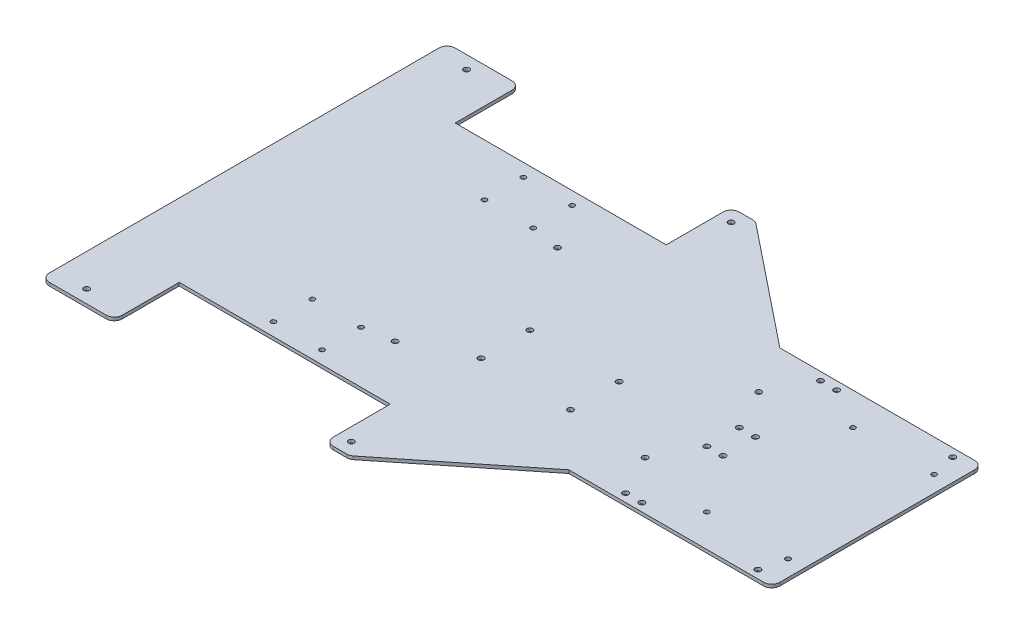
SolidWorks part; units mm, degrees
ref_plane "정면" through (0, 0, 0) normal (0, 0, 1) x (1, 0, 0)
ref_plane "윗면" through (0, 0, 0) normal (0, 1, 0) x (1, 0, 0)
ref_plane "우측면" through (0, 0, 0) normal (1, 0, 0) x (0, 0, -1)
sketch "스케치1" plane through (0, 0, 0) normal (0, 1, 0) x (1, 0, 0)
  line L1 (-195, -125) -> (195, -125)
  line L2 (-195, -125) -> (-195, 125)
  line L3 (-195, 125) -> (195, 125)
  line L4 (195, -125) -> (195, 125)
  line L5 (-195, -125) -> (195, 125) construction
  line L6 (-195, 125) -> (195, -125) construction
  point P0 (0, 0)
  dimension "D1" = 390
  dimension "D2" = 250
extrude "보스-돌출1" add sketch "스케치1" along normal blind 2
sketch "스케치2" plane through (0, 2, 0) normal (0, 1, 0) x (1, 0, 0)
  line L5 (195, 125) -> (-195, 125) construction
  line L6 (-150, 125) -> (-20, 125)
  line L7 (-150, 125) -> (-150, 85)
  line L8 (-150, 85) -> (-20, 85)
  line L9 (-20, 125) -> (-20, 85)
  line L10 (-150, -125) -> (-20, -125)
  line L11 (-150, -125) -> (-150, -85)
  line L12 (-150, -85) -> (-20, -85)
  line L13 (-20, -125) -> (-20, -85)
  line L14 (-195, -125) -> (195, -125) construction
  line L15 (70, 125) -> (195, 125)
  line L16 (70, 125) -> (70, 65)
  line L17 (70, 65) -> (195, 65)
  line L18 (195, 125) -> (195, 65)
  line L19 (70, -125) -> (195, -125)
  line L20 (70, -125) -> (70, -65)
  line L21 (70, -65) -> (195, -65)
  line L22 (195, -125) -> (195, -65)
  line L23 (195, -125) -> (195, 125) construction
  line L24 (-195, 125) -> (-195, -125) construction
  dimension "D1" = 130
  dimension "D2" = 40
  dimension "D3" = 40
  dimension "D4" = 60
  dimension "D5" = 60
  dimension "D6" = 45
  dimension "D7" = 125
extrude "컷-돌출1" cut sketch "스케치2" against normal blind 5
sketch "스케치3" plane through (0, 2, 0) normal (0, 1, 0) x (1, 0, 0)
  line L0 (-5, 125) -> (70, 65)
  line L2 (70, -65) -> (-5, -125)
  line L4 (-5, 125) -> (70, 125)
  line L5 (-5, -125) -> (70, -125)
  line L6 (70, -65) -> (70, -125)
  line L7 (70, 65) -> (70, 125)
  dimension "D1" = 75
  dimension "D2" = 75
extrude "컷-돌출2" cut sketch "스케치3" against normal blind 10
fillet "필렛1" radius 5 10 edges at (-20, 1, 125) (-20, 1, -125) (-5, 1, 125) (-5, 1, -125) (195, 1, -65) (195, 1, 65) (-195, 1, -125) (-195, 1, 125) (-150, 1, -125) (-150, 1, 125)
sketch "스케치4" plane through (0, 2, 0) normal (0, 1, 0) x (1, 0, 0)
  line L0 (-195, 0) -> (195, 0) construction
  line L1 (-100, 77) -> (-70, 77) construction
  line L2 (-100, 77) -> (-100, 53) construction
  line L3 (-100, 53) -> (-70, 53) construction
  line L4 (-70, 77) -> (-70, 53) construction
  line L5 (-100, 77) -> (-70, 53) construction
  line L6 (-100, 53) -> (-70, 77) construction
  line L7 (-195, 120) -> (-195, -120) construction
  line L8 (195, -60) -> (195, 60) construction
  line L9 (-150, 85) -> (-20, 85) construction
  line L10 (-100, -53) -> (-70, -77) construction
  line L11 (-100, -77) -> (-70, -53) construction
  line L12 (-70, -77) -> (-70, -53) construction
  line L13 (-100, -53) -> (-70, -53) construction
  line L14 (-100, -77) -> (-100, -53) construction
  line L15 (-100, -77) -> (-70, -77) construction
  line L17 (100, -60) -> (110, -60) construction
  line L18 (100, -60) -> (100, 60) construction
  line L19 (100, 60) -> (110, 60) construction
  line L20 (110, -60) -> (110, 60) construction
  line L21 (100, -60) -> (110, 60) construction
  line L22 (100, 60) -> (110, -60) construction
  line L23 (100, -10) -> (110, -10) construction
  line L24 (100, -10) -> (100, 10) construction
  line L25 (100, 10) -> (110, 10) construction
  line L26 (110, -10) -> (110, 10) construction
  line L27 (100, -10) -> (110, 10) construction
  line L28 (100, 10) -> (110, -10) construction
  circle A0 centre (-100, 77) radius 1.5
  circle A1 centre (-70, 77) radius 1.5
  circle A2 centre (-70, 53) radius 1.5
  circle A3 centre (-100, 53) radius 1.5
  circle A4 centre (-100, -53) radius 1.5
  circle A5 centre (-70, -53) radius 1.5
  circle A6 centre (-70, -77) radius 1.5
  circle A7 centre (-100, -77) radius 1.5
  circle A8 centre (100, 60) radius 1.75
  circle A9 centre (110, 60) radius 1.75
  circle A10 centre (100, 10) radius 1.75
  circle A11 centre (110, 10) radius 1.75
  circle A12 centre (100, -10) radius 1.75
  circle A13 centre (110, -10) radius 1.75
  circle A14 centre (100, -60) radius 1.75
  circle A15 centre (110, -60) radius 1.75
  point P0 (-85, 65)
  point P25 (-85, -65)
  point P26 (105, 0)
  point P31 (105, 0)
  dimension "D5" = 3
  dimension "D9" = 3.5
  dimension "D1" = 30
  dimension "D2" = 24
  dimension "D3" = 95
  dimension "D4" = 32
  dimension "D6" = 120
  dimension "D7" = 10
  dimension "D8" = 20
  dimension "D10" = 85
extrude "컷-돌출3" cut sketch "스케치4" against normal through all
sketch "스케치5" plane through (0, 2, 0) normal (0, 1, 0) x (1, 0, 0)
  line L0 (-20, -85) -> (-150, -85) construction
  line L1 (-16.5, -32.5) -> (38.5, -32.5) construction
  line L2 (-16.5, -32.5) -> (-16.5, -2.5) construction
  line L3 (-16.5, -2.5) -> (38.5, -2.5) construction
  line L4 (38.5, -32.5) -> (38.5, -2.5) construction
  line L5 (195, -60) -> (195, 60) construction
  circle A1 centre (-16.5, -2.5) radius 1.75
  circle A2 centre (38.5, -2.5) radius 1.75
  circle A3 centre (-16.5, -32.5) radius 1.75
  circle A4 centre (38.5, -32.5) radius 1.75
  dimension "D1" = 3.5
  dimension "D2" = 52.5
  dimension "D3" = 30
  dimension "D4" = 55
  dimension "D5" = 156.5
extrude "컷-돌출4" cut sketch "스케치5" against normal through all
sketch "스케치6" plane through (0, 2, 0) normal (0, 1, 0) x (1, 0, 0)
  line L0 (70, 65) -> (190, 65) construction
  line L1 (135, 45) -> (185, 45) construction
  line L2 (135, 45) -> (135, -45) construction
  line L3 (135, -45) -> (185, -45) construction
  line L4 (185, 45) -> (185, -45) construction
  line L5 (190, -65) -> (70, -65) construction
  line L6 (195, -60) -> (195, 60) construction
  circle A0 centre (135, 45) radius 1.5
  circle A1 centre (185, 45) radius 1.5
  circle A2 centre (135, -45) radius 1.5
  circle A3 centre (185, -45) radius 1.5
  dimension "D5" = 3
  dimension "D1" = 20
  dimension "D2" = 20
  dimension "D3" = 10
  dimension "D4" = 50
extrude "컷-돌출5" cut sketch "스케치6" against normal through all
sketch "스케치7" plane through (0, 2, 0) normal (0, 1, 0) x (1, 0, 0)
  line L0 (-6.7539, 125) -> (-15, 125) construction
  line L1 (-175, 117) -> (-12, 117) construction
  line L2 (-175, 117) -> (-175, -117) construction
  line L3 (-175, -117) -> (-12, -117) construction
  line L4 (-12, 117) -> (-12, -117) construction
  line L5 (-20, 85) -> (-20, 120) construction
  line L6 (-15, -125) -> (-6.7539, -125) construction
  line L7 (-52, 50) -> (-52, -50) construction
  line L8 (-195, 120) -> (-195, -120) construction
  line L9 (181.5, 60) -> (181.5, -60) construction
  line L10 (195, -60) -> (195, 60) construction
  line L11 (190, -65) -> (70, -65) construction
  line L12 (70, 65) -> (190, 65) construction
  line L13 (87, 35) -> (87, -35) construction
  line L14 (-150, 85) -> (-20, 85) construction
  line L15 (-20, -85) -> (-150, -85) construction
  circle A0 centre (-12, 117) radius 1.75
  circle A1 centre (-12, -117) radius 1.75
  circle A2 centre (181.5, 60) radius 1.75
  circle A3 centre (181.5, -60) radius 1.75
  circle A4 centre (-175, 117) radius 1.75
  circle A5 centre (-175, -117) radius 1.75
  circle A6 centre (87, 35) radius 1.75
  circle A7 centre (87, -35) radius 1.75
  circle A9 centre (-52, 50) radius 1.75
  circle A10 centre (-52, -50) radius 1.75
  dimension "D1" = 8
  dimension "D2" = 8
  dimension "D3" = 8
  dimension "D4" = 20
  dimension "D5" = 3.5
  dimension "D7" = 5
  dimension "D8" = 5
  dimension "D10" = 30
  dimension "D11" = 108
  dimension "D13" = 35
  dimension "D14" = 35
  dimension "D6" = 13.5
  dimension "D9" = 70
  dimension "D12" = 40
extrude "컷-돌출6" cut sketch "스케치7" against normal through all
